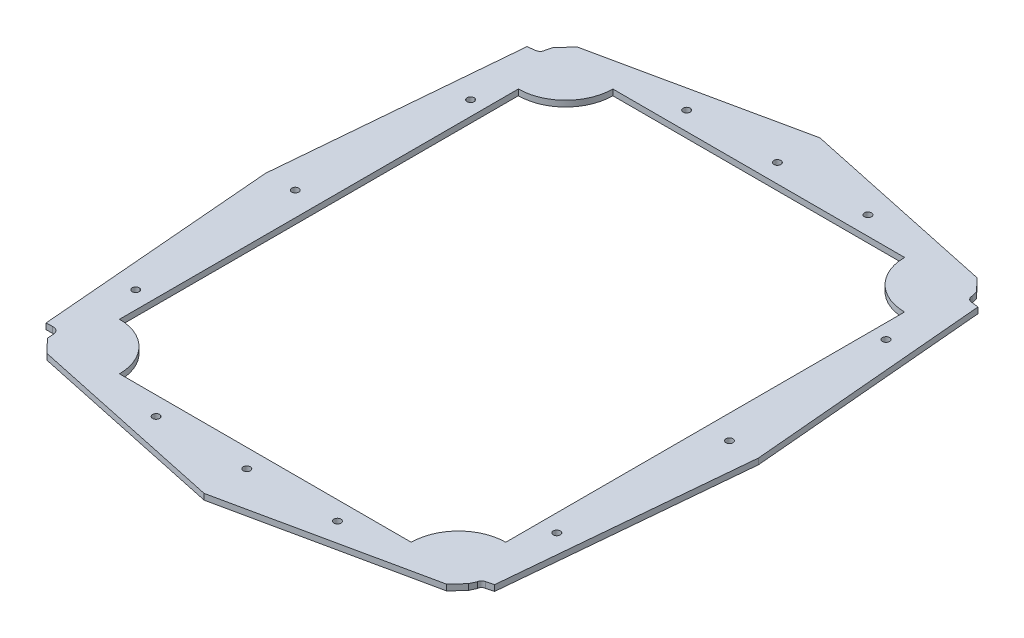
SolidWorks part; units mm, degrees
ref_plane "Front Plane" through (0, 0, 0) normal (0, 0, 1) x (1, 0, 0)
ref_plane "Top Plane" through (0, 0, 0) normal (0, 1, 0) x (1, 0, 0)
ref_plane "Right Plane" through (0, 0, 0) normal (1, 0, 0) x (0, 0, -1)
sketch "Sketch1" plane through (0, -125.1639, 0) normal (0, -1, 0) x (-1, 0, 0)
  line L39 (0, 165.5699) -> (-107.5, 142.6399) construction
  line L40 (-107.5, 142.6399) -> (-132.5632, 0) construction
  line L41 (-132.5632, 0) -> (-107.5, -142.6399) construction
  line L42 (-107.5, -142.6399) -> (0, -165.5699) construction
  line L47 (0, -165.5699) -> (107.5, -142.6399) construction
  line L48 (107.5, -142.6399) -> (132.5632, 0) construction
  line L49 (132.5632, 0) -> (107.5, 142.6399) construction
  line L50 (107.5, 142.6399) -> (0, 165.5699) construction
  line L51 (-107.5, 142.6399) -> (-132.5632, 0)
  line L52 (-132.5632, 0) -> (-107.5, -142.6399)
  line L53 (-107.5, -142.6399) -> (0, -165.5699)
  line L54 (0, -165.5699) -> (107.5, -142.6399)
  line L55 (107.5, -142.6399) -> (132.5632, 0)
  line L56 (132.5632, 0) -> (107.5, 142.6399)
  line L57 (107.5, 142.6399) -> (0, 165.5699)
  line L58 (0, 165.5699) -> (-107.5, 142.6399)
  line L82 (-97.5, -132.6399) -> (97.5, -132.6399) construction
  line L83 (-91.15, 126.2899) -> (91.15, 126.2899)
  line L84 (-91.15, 126.2899) -> (-91.15, -126.2899)
  line L85 (-91.15, -126.2899) -> (91.15, -126.2899)
  line L86 (91.15, 126.2899) -> (91.15, -126.2899)
  line L87 (-91.15, 126.2899) -> (91.15, -126.2899) construction
  line L88 (-91.15, -126.2899) -> (91.15, 126.2899) construction
  line L89 (-97.5, -132.6399) -> (-97.5, 132.6399) construction
  circle A0 centre (-111.6902, 89.4108) radius 1.8987 construction
  circle A1 centre (-116.75, 0.1657) radius 1.8987 construction
  circle A2 centre (-113.2269, -89.1534) radius 1.8987 construction
  circle A3 centre (-48.75, -142.6399) radius 1.8987 construction
  circle A4 centre (0, -142.6399) radius 1.8987 construction
  circle A5 centre (48.75, -142.6399) radius 1.8987 construction
  circle A6 centre (113.2269, -89.1534) radius 1.8692 construction
  circle A7 centre (116.75, 0.1657) radius 1.8986 construction
  circle A8 centre (111.6902, 89.4108) radius 1.8987 construction
  circle A9 centre (48.75, 142.6399) radius 1.8987 construction
  circle A10 centre (0, 142.6399) radius 1.8987 construction
  circle A11 centre (-48.75, 142.6399) radius 1.8987 construction
  circle A12 centre (-111.6902, 89.4108) radius 1.8987
  circle A13 centre (-116.75, 0.1657) radius 1.8987
  circle A14 centre (-113.2269, -89.1534) radius 1.8987
  circle A15 centre (-48.75, -142.6399) radius 1.8987
  circle A16 centre (0, -142.6399) radius 1.8987
  circle A17 centre (48.75, -142.6399) radius 1.8987
  circle A18 centre (113.2269, -89.1534) radius 1.8692
  circle A19 centre (116.75, 0.1657) radius 1.8987
  circle A20 centre (111.6902, 89.4108) radius 1.8987
  circle A21 centre (48.75, 142.6399) radius 1.8987
  circle A22 centre (0, 142.6399) radius 1.8987
  circle A23 centre (-48.75, 142.6399) radius 1.8987
  point P4 (0, 0)
  dimension "D1" = 6.35
  dimension "D2" = 6.35
extrude "Boss-Extrude1" add sketch "Sketch1" along normal blind 3.175
sketch "Sketch2" plane through (0, -128.3389, 0) normal (0, -1, 0) x (1, 0, 0)
  line L0 (-91.15, -126.2899) -> (91.15, -126.2899) construction
  line L1 (91.15, -126.2899) -> (103.85, -126.2899)
  line L2 (91.15, -126.2899) -> (91.15, 126.2899)
  line L3 (91.15, 126.2899) -> (103.85, 126.2899)
  line L4 (103.85, -126.2899) -> (103.85, 126.2899)
  line L5 (91.15, -126.2899) -> (91.15, 126.2899) construction
  line L7 (-91.15, -126.2899) -> (-103.85, -126.2899)
  line L8 (0, -165.5699) -> (107.5, -142.6399)
  line L9 (107.5, -142.6399) -> (132.5632, 0)
  line L10 (132.5632, 0) -> (107.5, 142.6399)
  line L11 (107.5, 142.6399) -> (0, 165.5699)
  line L12 (0, 165.5699) -> (-107.5, 142.6399)
  line L13 (-107.5, 142.6399) -> (-132.5632, 0)
  line L14 (-132.5632, 0) -> (-107.5, -142.6399)
  line L15 (-107.5, -142.6399) -> (0, -165.5699)
  line L16 (0, -165.5699) -> (107.5, -142.6399)
  line L17 (107.5, -142.6399) -> (132.5632, 0)
  line L18 (132.5632, 0) -> (107.5, 142.6399)
  line L19 (107.5, 142.6399) -> (0, 165.5699)
  line L20 (0, 165.5699) -> (-107.5, 142.6399)
  line L21 (-107.5, 142.6399) -> (-132.5632, 0)
  line L22 (-132.5632, 0) -> (-107.5, -142.6399)
  line L23 (-107.5, -142.6399) -> (0, -165.5699)
  line L24 (-91.15, -126.2899) -> (-91.15, 126.2899)
  line L25 (-91.15, 126.2899) -> (-103.85, 126.2899)
  line L26 (-103.85, -126.2899) -> (-103.85, 126.2899)
  line L27 (-91.15, -126.2899) -> (91.15, -126.2899)
  line L28 (-91.15, -126.2899) -> (-91.15, -132.6399)
  line L29 (-91.15, -132.6399) -> (91.15, -132.6399)
  line L30 (91.15, -126.2899) -> (91.15, -132.6399)
  line L31 (91.15, 126.2899) -> (-91.15, 126.2899)
  line L32 (91.15, 126.2899) -> (91.15, 132.6399)
  line L33 (91.15, 132.6399) -> (-91.15, 132.6399)
  line L34 (-91.15, 126.2899) -> (-91.15, 132.6399)
  line L35 (91.15, -126.2899) -> (103.85, -126.2899)
  line L36 (91.15, -126.2899) -> (91.15, -132.6399)
  line L37 (91.15, -132.6399) -> (103.85, -132.6399)
  line L38 (103.85, -126.2899) -> (103.85, -132.6399)
  line L39 (-91.15, -132.6399) -> (-103.85, -132.6399)
  line L40 (-91.15, -132.6399) -> (-91.15, -126.2899)
  line L41 (-91.15, -126.2899) -> (-103.85, -126.2899)
  line L42 (-103.85, -132.6399) -> (-103.85, -126.2899)
  line L43 (-91.15, 132.6399) -> (-103.85, 132.6399)
  line L44 (-91.15, 132.6399) -> (-91.15, 126.2899)
  line L45 (-91.15, 126.2899) -> (-103.85, 126.2899)
  line L46 (-103.85, 132.6399) -> (-103.85, 126.2899)
  line L47 (91.15, 132.6399) -> (103.85, 132.6399)
  line L48 (91.15, 132.6399) -> (91.15, 126.2899)
  line L49 (91.15, 126.2899) -> (103.85, 126.2899)
  line L50 (103.85, 132.6399) -> (103.85, 126.2899)
  line M28 (91.15, -126.2899) -> (-91.15, -126.2899)
  line M30 (-91.15, 126.2899) -> (91.15, 126.2899)
  dimension "D2" = 12.7
  dimension "D3" = 12.7
  dimension "D4" = 6.35
  dimension "D5" = 6.35
  dimension "D1" = 0
extrude "Cut-Extrude1" cut sketch "Sketch2" against normal up to surface (3.175 mm away) contours L34 L32 L33 M30 | L30 L28 L29 M28 | L50 L47 L32 L3 | L43 L46 L25 L34 | L42 L39 L28 L7 | L38 L1 L30 L37 | L2 L1 L4 L3 | L24 L7 L26 L25 region at (0, -128.3389, -129.4649) region at (97.5, -128.3389, -129.4649) region at (97.5, -128.3389, 129.4649) region at (0, -128.3389, 129.4649) region at (-97.5, -128.3389, -129.4649) region at (-97.5, -128.3389, 129.4649) up to face at (0, -125.1639, 0)
sketch "Sketch3" plane through (0, -128.3389, 0) normal (0, -1, 0) x (1, 0, 0)
  line L0 (-114.645, -132.6399) -> (-103.85, -132.6399)
  line L1 (-114.645, 132.2063) -> (-103.85, 132.6399)
  line L2 (114.645, 133.1139) -> (103.85, 132.6399)
  line L3 (114.645, -132.6399) -> (103.85, -132.6399)
  line L4 (-103.85, -132.6399) -> (-114.645, -132.6399)
  line L5 (103.85, -132.6399) -> (114.645, -132.6399)
  line L6 (-103.85, 132.6399) -> (-114.645, 132.2063)
  line L7 (103.85, 132.6399) -> (114.645, 133.1139)
  line L8 (0, -165.5699) -> (107.5, -142.6399)
  line L9 (107.5, -142.6399) -> (132.5632, 0)
  line L10 (132.5632, 0) -> (107.5, 142.6399)
  line L11 (107.5, 142.6399) -> (0, 165.5699)
  line L12 (0, 165.5699) -> (-107.5, 142.6399)
  line L13 (-107.5, 142.6399) -> (-132.5632, 0)
  line L14 (-132.5632, 0) -> (-107.5, -142.6399)
  line L15 (-107.5, -142.6399) -> (0, -165.5699)
  line L16 (0, -165.5699) -> (107.5, -142.6399)
  line L17 (107.5, -142.6399) -> (132.5632, 0)
  line L18 (132.5632, 0) -> (107.5, 142.6399)
  line L19 (107.5, 142.6399) -> (0, 165.5699)
  line L20 (0, 165.5699) -> (-107.5, 142.6399)
  line L21 (-107.5, 142.6399) -> (-132.5632, 0)
  line L22 (-132.5632, 0) -> (-107.5, -142.6399)
  line L23 (-107.5, -142.6399) -> (0, -165.5699)
  line L24 (113.0935, 136.508) -> (114.645, 133.1139)
  line L25 (120.6111, 129.9136) -> (116.8523, 131.0014)
  line L26 (113.0935, 136.508) -> (114.645, 133.1139)
  line L27 (113.7573, -135.9554) -> (114.645, -132.6399)
  line L28 (-132.5632, 0) -> (-103.85, 0)
  line L29 (-103.85, 132.6399) -> (-103.85, -132.6399) construction
  line L30 (121.2427, -129.3244) -> (117.5, -129.7849)
  line L31 (-113.7573, -135.9554) -> (-114.645, -132.6399)
  line L32 (-132.5632, 0) -> (-143.728, 0)
  line L33 (-121.2427, -129.3244) -> (-117.5, -129.7849)
  line L34 (-114.4184, 135.3995) -> (-114.645, 132.2063)
  line L35 (-121.8714, 128.7321) -> (-118.1449, 128.5631)
  line L42 (107.5, -142.6399) -> (113.7573, -135.9554)
  line L43 (121.2427, -129.3244) -> (132.5632, 0)
  line L44 (120.6111, 129.9136) -> (132.5632, 0)
  line L45 (113.0935, 136.508) -> (107.5, 142.6399)
  line L46 (-107.5, 142.6399) -> (-114.4184, 135.3995)
  line L47 (-121.8714, 128.7321) -> (-132.5632, 0)
  line L48 (-132.5632, 0) -> (-121.2427, -129.3244)
  line L49 (-113.7573, -135.9554) -> (-107.5, -142.6399)
  circle A0 centre (116.8523, 133.2108) radius 2.2094
  circle A1 centre (117.5, -132.6399) radius 2.855
  circle A2 centre (-117.5, -132.6399) radius 2.855
  circle A3 centre (-118.1449, 132.0658) radius 3.5027
  arc A6 (121.2427, -129.3244) -> (113.7573, -135.9554) centre (117.5, -132.6399) ccw construction
  arc A7 (121.2427, -129.3244) -> (113.7573, -135.9554) centre (117.5, -132.6399) ccw
  arc A8 (-113.7573, -135.9554) -> (-121.2427, -129.3244) centre (-117.5, -132.6399) ccw construction
  arc A9 (-113.7573, -135.9554) -> (-121.2427, -129.3244) centre (-117.5, -132.6399) ccw
  arc A10 (-121.8714, 128.7321) -> (-114.4184, 135.3995) centre (-118.1449, 132.0658) ccw construction
  arc A11 (-121.8714, 128.7321) -> (-114.4184, 135.3995) centre (-118.1449, 132.0658) ccw
  arc A12 (113.0935, 136.508) -> (120.6111, 129.9136) centre (116.8523, 133.2108) ccw construction
  arc A13 (113.0935, 136.508) -> (120.6111, 129.9136) centre (116.8523, 133.2108) ccw
  line M21 (107.5, -142.6399) -> (132.5632, 0)
  line M22 (132.5632, 0) -> (107.5, 142.6399)
  line M25 (-107.5, 142.6399) -> (-132.5632, 0)
  line M26 (-132.5632, 0) -> (-107.5, -142.6399)
  dimension "D2" = 39.878
  dimension "D3" = 10.795
  dimension "D4" = 10.795
  dimension "D5" = 10.795
  dimension "D6" = 10.795
  dimension "D1" = 0
extrude "Boss-Extrude2" add sketch "Sketch3" against normal up to surface (3.175 mm away) contours A11 L47 L6 M25 | A11 L6 L46 M25 | L1 A11 L34 | L35 A11 L1 A3 | A13 L45 L7 M22 | L24 A13 L2 | L2 A13 L25 A0 | A13 L7 L44 M22 | A7 L43 L5 M21 | A7 L5 L42 M21 | L3 A7 L27 | L30 A7 L3 A1 | A9 L4 L48 M26 | A9 L49 L4 M26 | L31 A9 L0 | L0 A9 L33 A2 region at (-116.0627, -128.3389, -129.7093) region at (-113.5221, -128.3389, -133.852) region at (-121.1094, -128.3389, -86.386) region at (-110.3969, -128.3389, -136.5518) region at (-121.3167, -128.3389, 86.1628) region at (-110.6777, -128.3389, 136.2592) region at (-120.1713, -128.3389, 128.5533) region at (110.3969, -128.3389, -136.5518) region at (-113.984, -128.3389, 133.4191) region at (121.1094, -128.3389, -86.386) region at (113.5221, -128.3389, -133.852) region at (116.0627, -128.3389, -129.7093) region at (120.901, -128.3389, 86.6109) region at (110.1104, -128.3389, 136.8585) region at (115.5972, -128.3389, 130.3842) region at (113.0632, -128.3389, 134.2979)
sketch "Sketch4" plane through (0, -125.1639, 0) normal (0, 1, 0) x (1, 0, 0)
  line L20 (107.5, 142.6399) -> (0, 165.5699)
  line L21 (0, 165.5699) -> (-107.5, 142.6399)
  line L22 (-107.5, 142.6399) -> (-113.7573, 135.9554)
  line L23 (-113.7573, 135.9554) -> (-114.645, 132.6399)
  line L24 (-117.5, 129.7849) -> (-121.2427, 129.3244)
  line L25 (-121.2427, 129.3244) -> (-132.5632, 0)
  line L26 (-132.5632, 0) -> (-121.8714, -128.7321)
  line L27 (-121.8714, -128.7321) -> (-118.462, -128.5774)
  line L28 (-114.645, -132.2063) -> (-114.4184, -135.3995)
  line L29 (-114.4184, -135.3995) -> (-107.5, -142.6399)
  line L30 (-107.5, -142.6399) -> (0, -165.5699)
  line L31 (0, -165.5699) -> (107.5, -142.6399)
  line L32 (107.5, -142.6399) -> (113.0935, -136.508)
  line L33 (113.0935, -136.508) -> (114.645, -133.1139)
  line L34 (116.8523, -131.0014) -> (120.6111, -129.9136)
  line L35 (120.6111, -129.9136) -> (132.5632, 0)
  line L36 (132.5632, 0) -> (121.2427, 129.3244)
  line L37 (121.2427, 129.3244) -> (117.5, 129.7849)
  line L38 (114.645, 132.6399) -> (113.7573, 135.9554)
  line L39 (113.7573, 135.9554) -> (107.5, 142.6399)
  line L40 (107.5, 142.6399) -> (0, 165.5699)
  line L41 (0, 165.5699) -> (-107.5, 142.6399)
  line L42 (-107.5, 142.6399) -> (-113.7573, 135.9554)
  line L43 (-113.7573, 135.9554) -> (-114.645, 132.6399)
  line L44 (-117.5, 129.7849) -> (-121.2427, 129.3244)
  line L45 (-121.2427, 129.3244) -> (-132.5632, 0)
  line L46 (-132.5632, 0) -> (-121.8714, -128.7321)
  line L47 (-121.8714, -128.7321) -> (-118.462, -128.5774)
  line L48 (-114.645, -132.2063) -> (-114.4184, -135.3995)
  line L49 (-114.4184, -135.3995) -> (-107.5, -142.6399)
  line L50 (-107.5, -142.6399) -> (0, -165.5699)
  line L51 (0, -165.5699) -> (107.5, -142.6399)
  line L52 (107.5, -142.6399) -> (113.0935, -136.508)
  line L53 (113.0935, -136.508) -> (114.645, -133.1139)
  line L54 (116.8523, -131.0014) -> (120.6111, -129.9136)
  line L55 (120.6111, -129.9136) -> (132.5632, 0)
  line L56 (132.5632, 0) -> (121.2427, 129.3244)
  line L57 (121.2427, 129.3244) -> (117.5, 129.7849)
  line L58 (114.645, 132.6399) -> (113.7573, 135.9554)
  line L59 (113.7573, 135.9554) -> (107.5, 142.6399)
  arc A0 (-122.4652, 115.3588) -> (-83.4482, 147.7702) centre (-103.85, 132.6399) ccw
  arc A1 (83.4482, 147.7702) -> (122.4652, 115.3588) centre (103.85, 132.6399) ccw
  arc A2 (-83.4482, -147.7702) -> (-122.9385, -115.8832) centre (-103.85, -132.6399) ccw
  arc A3 (121.9955, -114.8662) -> (83.4482, -147.7702) centre (103.85, -132.6399) ccw
  arc A4 (-117.5, 129.7849) -> (-114.645, 132.6399) centre (-117.5, 132.6399) ccw
  arc A5 (-114.645, -132.2063) -> (-118.462, -128.5774) centre (-118.1449, -132.0658) ccw
  arc A6 (116.8523, -131.0014) -> (114.645, -133.1139) centre (116.8523, -133.2108) ccw
  arc A7 (114.645, 132.6399) -> (117.5, 129.7849) centre (117.5, 132.6399) ccw
  arc A8 (-117.5, 129.7849) -> (-114.645, 132.6399) centre (-117.5, 132.6399) ccw
  arc A9 (-114.645, -132.2063) -> (-118.462, -128.5774) centre (-118.1449, -132.0658) ccw
  arc A10 (116.8523, -131.0014) -> (114.645, -133.1139) centre (116.8523, -133.2108) ccw
  arc A11 (114.645, 132.6399) -> (117.5, 129.7849) centre (117.5, 132.6399) ccw
  line M28 (103.85, 132.6399) -> (103.85, -132.6399)
  line M29 (103.85, -132.6399) -> (-103.85, -132.6399)
  line M30 (-103.85, -132.6399) -> (-103.85, 132.6399)
  line M31 (-103.85, 132.6399) -> (103.85, 132.6399)
  dimension "D1" = 0
extrude "Boss-Extrude3" add sketch "Sketch4" against normal up to surface (3.175 mm away) contours A0 M30 M31 | A1 M31 M28 | A2 M29 M30 | A3 M28 M29 region at (93.0699, -125.1639, -121.8598) region at (-93.0699, -125.1639, -121.8598) region at (93.0699, -125.1639, 121.8598) region at (-93.0699, -125.1639, 121.8598) up to face at (0, -128.3389, 0)
